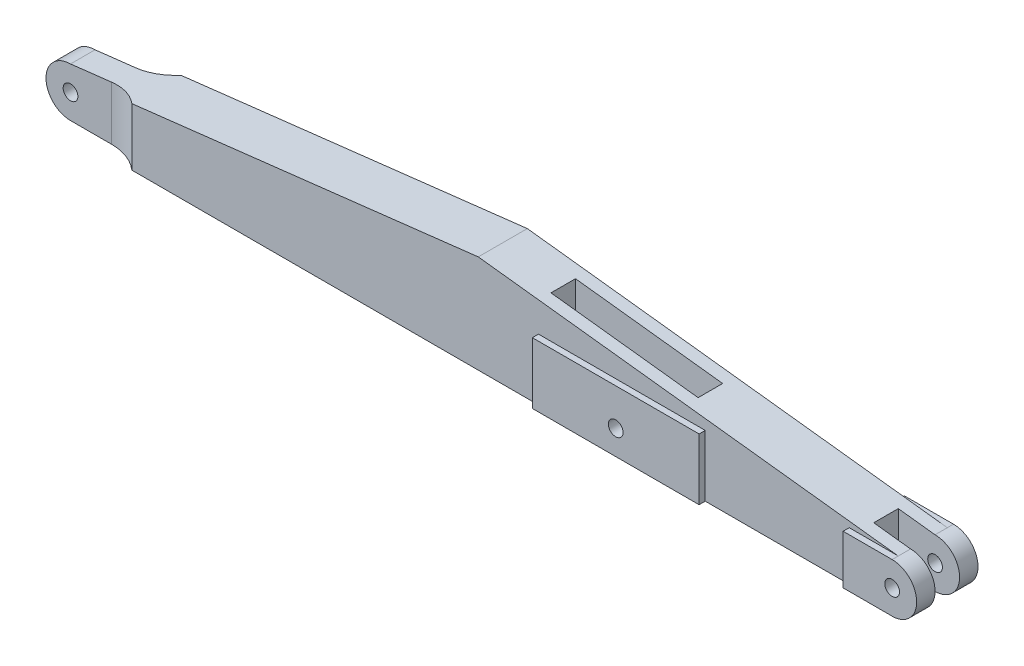
SolidWorks part; units mm, degrees
ref_plane "Alzado" through (0, 0, 0) normal (0, 0, 1) x (1, 0, 0)
ref_plane "Planta" through (0, 0, 0) normal (0, 1, 0) x (1, 0, 0)
ref_plane "Vista lateral" through (0, 0, 0) normal (1, 0, 0) x (0, 0, -1)
sketch "Croquis1" plane through (0, 0, 0) normal (0, 0, 1) x (1, 0, 0)
  line L0 (0, 0) -> (171.25, 0) construction
  line L2 (0, -5) -> (171.25, -5)
  line L3 (85.625, 0) -> (85.625, 15) construction
  line L4 (0, 5) -> (85.625, 15)
  line L5 (85.625, 15) -> (171.25, 5)
  arc A0 (0, 5) -> (0, -5) centre (0, 0) ccw
  arc A1 (171.25, -5) -> (171.25, 5) centre (171.25, 0) ccw
  circle A2 centre (171.25, 0) radius 1.5
  circle A3 centre (0, 0) radius 1.5
  circle A4 centre (114.8955, 0) radius 1.5
  point P3 (85.625, 0)
  dimension "D2" = 5
  dimension "D3" = 3
  dimension "D5" = 3
  dimension "D1" = 171.25
  dimension "D4" = 15
  dimension "D6" = 114.8955
extrude "Saliente-Extruir1" add sketch "Croquis1" along normal blind 10
ref_plane "Plano1" through (0, 0, 5) normal (0, 0, 1) x (1, 0, 0)
sketch "Croquis2" plane through (0, 0, 5) normal (0, 0, 1) x (1, 0, 0)
  line L1 (171.25, 5) -> (161.25, 5)
  line L3 (171.25, -5) -> (161.25, -5)
  line L4 (161.25, 5) -> (161.25, -5)
  line L6 (114.8955, 0) -> (114.8955, -11.5853) construction
  line L10 (97.8955, -5) -> (131.8955, -5)
  line L11 (97.8955, -5) -> (97.8955, 7.5)
  line L12 (97.8955, 7.5) -> (131.8955, 7.5)
  line L13 (131.8955, -5) -> (131.8955, 7.5)
  arc A0 (171.25, -5) -> (171.25, 5) centre (171.25, 0) ccw construction
  arc A1 (171.25, -5) -> (171.25, 5) centre (171.25, 0) ccw
  circle A2 centre (171.25, 0) radius 1.5 construction
  circle A3 centre (171.25, 0) radius 1.5
  circle A4 centre (114.8955, 0) radius 1.5
  dimension "D2" = 34
  dimension "D1" = 10
  dimension "D3" = 17
  dimension "D4" = 12.5
extrude "Saliente-Extruir2" add sketch "Croquis2" along normal mid plane 12.5
sketch "Croquis3" plane through (0, -5, 0) normal (0, -1, 0) x (1, 0, 0)
  line L2 (176.25, 11.25) -> (176.25, -1.25) construction
  line L3 (163.75, 2.5) -> (188.75, 2.5)
  line L4 (163.75, 2.5) -> (163.75, 7.5)
  line L5 (163.75, 7.5) -> (188.75, 7.5)
  line L6 (188.75, 2.5) -> (188.75, 7.5)
  line L7 (163.75, 2.5) -> (188.75, 7.5) construction
  line L8 (163.75, 7.5) -> (188.75, 2.5) construction
  point P0 (176.25, 5)
  dimension "D1" = 5
  dimension "D2" = 25
  dimension "D3" = 12.5
  dimension "D4" = 6.25
extrude "Cortar-Extruir1" cut sketch "Croquis3" against normal blind 15
sketch "Croquis4" plane through (0, -5, 0) normal (0, -1, 0) x (1, 0, 0)
  line L0 (163.75, 5) -> (112.9437, 5) construction
  line L1 (163.75, 7.5) -> (163.75, 2.5) construction
  line L2 (11, 5) -> (-11, 5) construction
  line L3 (0, 10) -> (97.8955, 10) construction
  line L4 (97.9437, 2.5) -> (127.9437, 2.5)
  line L5 (97.9437, 2.5) -> (97.9437, 7.5)
  line L6 (97.9437, 7.5) -> (127.9437, 7.5)
  line L7 (127.9437, 2.5) -> (127.9437, 7.5)
  line L8 (97.9437, 2.5) -> (127.9437, 7.5) construction
  line L9 (97.9437, 7.5) -> (127.9437, 2.5) construction
  line L10 (0, 0) -> (97.8955, 0) construction
  line L11 (112.9437, 5) -> (112.9437, 18.6776) construction
  point P6 (112.9437, 5)
  dimension "D1" = 5
  dimension "D2" = 30
  dimension "D3" = 2.5
  dimension "D4" = 2.5
extrude "Cortar-Extruir2" cut sketch "Croquis4" against normal blind 30
sketch "Croquis6" plane through (0, -5, 0) normal (0, -1, 0) x (1, 0, 0)
  line L0 (-5, 10) -> (-5, 0) construction
  line L1 (15, 7.5) -> (15, 15.1627)
  line L2 (-25, 2.5) -> (15, 2.5)
  line L3 (-25, 7.5) -> (-25, 15.1627)
  line L4 (-25, 7.5) -> (15, 7.5)
  line L6 (-25, 2.5) -> (15, 7.5) construction
  line L7 (-25, 7.5) -> (15, 2.5) construction
  line L8 (-25, -5.1627) -> (15, -5.1627)
  line L9 (-25, -5.1627) -> (-25, 2.5)
  line L10 (-25, 15.1627) -> (15, 15.1627)
  line L11 (15, -5.1627) -> (15, 2.5)
  line L12 (-25, -5.1627) -> (15, 15.1627) construction
  line L13 (-25, 15.1627) -> (15, -5.1627) construction
  point P4 (-5, 5)
  point P9 (-5, 5)
  dimension "D1" = 5
  dimension "D2" = 40
extrude "Cortar-Extruir3" cut sketch "Croquis6" against normal blind 60
fillet "Redondeo1" radius 10 2 edges at (15, 0.8759, 2.5) (15, 0.8759, 7.5)
sketch "Croquis8" plane through (0, 0, 5) normal (0, 0, 1) x (1, 0, 0)
  point P0 (114.8955, 0)
